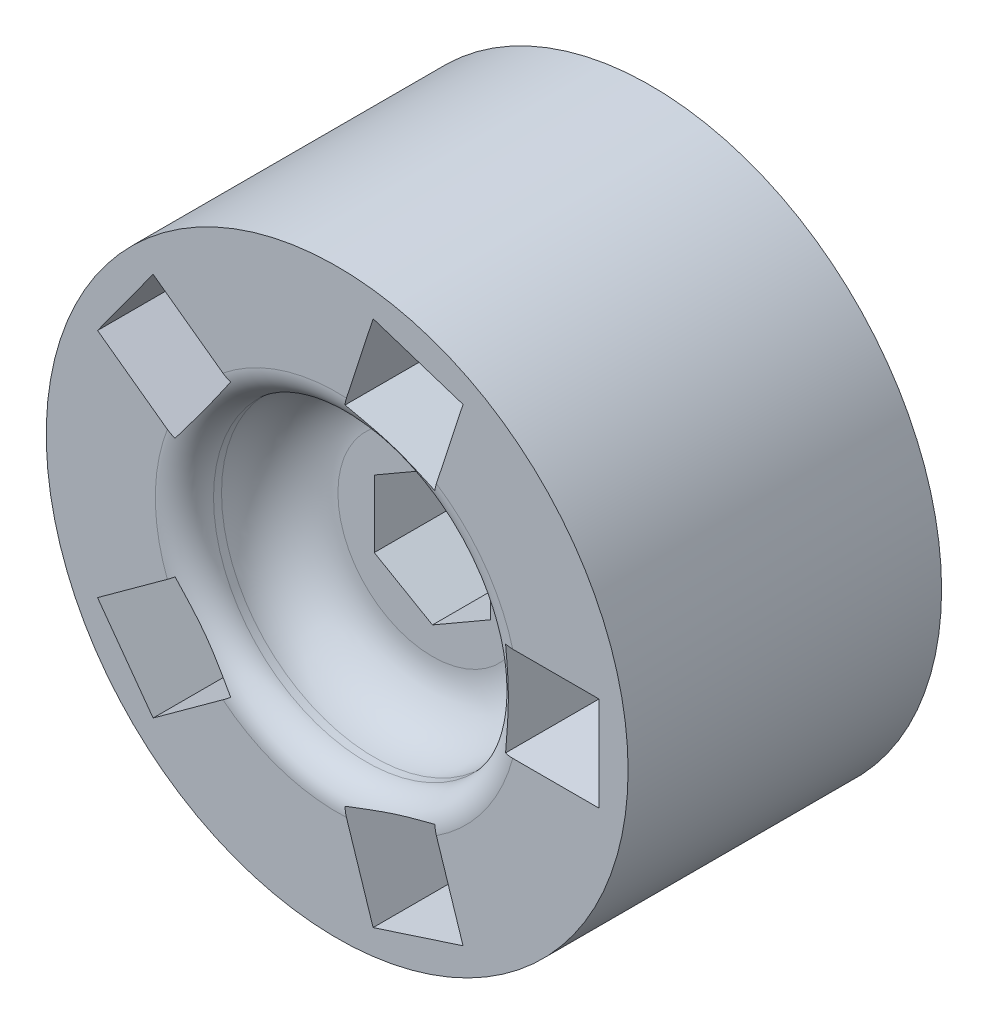
SolidWorks part; units mm, degrees
ref_plane "Front Plane" through (0, 0, 0) normal (0, 0, 1) x (1, 0, 0)
ref_plane "Top Plane" through (0, 0, 0) normal (0, 1, 0) x (1, 0, 0)
ref_plane "Right Plane" through (0, 0, 0) normal (1, 0, 0) x (0, 0, -1)
sketch "Sketch1" plane through (0, 0, 0) normal (0, 0, 1) x (1, 0, 0)
  circle A0 centre (-11.8226, 14.5298) radius 20
  circle A1 centre (-11.8226, 14.5298) radius 1
  dimension "D1" = 40
  dimension "D2" = 2
extrude "Boss-Extrude1" add sketch "Sketch1" along normal blind 21.55
hole_wizard "Tap Drill for M5x0.8 Tap1" positions "Sketch2" profile "Sketch3" hole size "M5x0.8" standard "ANSI Metric"
sketch "Sketch2" plane through (0, 0, 21.55) normal (0, 0, 1) x (1, 0, 0)
  point P0 (-11.8226, 14.5298)
sketch "Sketch3" plane through (-11.8226, 14.5298, 21.55) normal (1, 0, 0) x (0, -1, 0)
  line L0 (0, 0) -> (0, 6.2618)
  line L1 (0, 6.2618) -> (2.1, 5)
  line L2 (2.1, 5) -> (2.1, 0)
  line L5 (2.1, 0) -> (0, 0)
  line L10 (0, 6.2618) -> (-2.1, 5) construction
  line L11 (0, -6.35) -> (0, 107.95) construction
  dimension "Hole Dia." = 4.2
  dimension "Hole Depth" = 5
  dimension "Drill Angle" = 118
sketch "Sketch4" plane through (0, 0, 21.55) normal (0, 0, 1) x (1, 0, 0)
  line L1 (6.1774, 17.7798) -> (-0.3226, 17.7798)
  line L2 (6.1774, 17.7798) -> (6.1774, 11.2798)
  line L3 (6.1774, 11.2798) -> (-0.3226, 11.2798)
  line L4 (-0.3226, 17.7798) -> (-0.3226, 11.2798)
  circle A0 centre (-11.8226, 14.5298) radius 1 construction
  circle A1 centre (-11.8226, 14.5298) radius 20 construction
  dimension "D1" = 6.5
  dimension "D2" = 6.5
  dimension "D3" = 3.25
  dimension "D4" = 18
extrude "Cut-Extrude1" cut sketch "Sketch4" against normal offset from surface (19.05 mm away) 2.5 up to face at (8.1774, 14.5298, 0)
ref_axis "Axis1" through (-11.8226, 14.5298, 21.55) along (0, 0, -1)
pattern_circular "CirPattern1" count 5 over 360 about axis through (-11.8226, 14.5298, 21.55) along (0, 0, -1) of "Cut-Extrude1"
sketch "Sketch5" plane through (0, 0, 0) normal (0, 0, -1) x (-1, 0, 0)
  circle A0 centre (11.8226, 14.5298) radius 5
  circle A1 centre (11.8226, 14.5298) radius 6
  dimension "D1" = 10
  dimension "D2" = 12
extrude "Cut-Extrude2" cut sketch "Sketch5" against normal blind 1
fillet "Fillet3" radius 0.5 2 edges at (-16.8226, 14.5298, 1) (-17.8226, 14.5298, 1)
sketch "Sketch6" plane through (0, 0, 21.55) normal (0, 0, 1) x (1, 0, 0)
  line L0 (-15.8226, 16.8388) -> (-11.8226, 19.1465)
  line L1 (-7.8226, 12.2208) -> (-15.8226, 12.2208)
  line L2 (-7.8226, 12.2208) -> (-7.8226, 16.8388)
  line L3 (-7.8226, 16.8388) -> (-15.8226, 16.8388)
  line L4 (-15.8226, 12.2208) -> (-15.8226, 16.8388)
  line L5 (-7.8226, 12.2208) -> (-15.8226, 16.8388) construction
  line L6 (-7.8226, 16.8388) -> (-15.8226, 12.2208) construction
  line L7 (-11.8226, 19.1465) -> (-7.8226, 16.8388)
  line L8 (-7.8226, 12.2208) -> (-11.8226, 9.913)
  line L9 (-11.8226, 9.913) -> (-15.8226, 12.2208)
  point P0 (-11.8226, 14.5298)
  circle M25 centre (-11.8226, 14.5298) radius 2.1
  dimension "D1" = 8
  dimension "D2" = 4.618
  dimension "D3" = 4.618
  dimension "D4" = 4.618
  dimension "D5" = 4.618
  dimension "D6" = 4.618
extrude "Cut-Extrude3" cut sketch "Sketch6" against normal up to surface (21.55 mm away) contours L4 L1 L2 L3 M25 | M25 | L7 L0 L3 | L9 L8 L1 region at (-11.8226, 17.608, 21.55) region at (-11.8226, 16.7464, 21.55) region at (-11.8226, 11.4515, 21.55) region at (-11.8226, 14.5298, 21.55) up to face at (-17.8226, 14.5298, 0)
sketch "Sketch7" plane through (0, 0, 21.55) normal (0, 0, 1) x (1, 0, 0)
  circle A0 centre (-11.8226, 14.5298) radius 10.5
  dimension "D1" = 21
extrude "Cut-Extrude4" cut sketch "Sketch7" against normal offset from surface (6.55 mm away) 15 up to face at (-17.8226, 14.5298, 0)
fillet "Fillet4" radius 2 1 edges at (-1.3226, 14.5298, 21.55)
fillet "Fillet5" radius 4 1 edges at (-1.3226, 14.5298, 15)
equation "\"D2@Sketch4\"=6.5"
equation "\"D3@Sketch4\"=6.5/2"
equation "\"oringdiameter\"= 11"
equation "\"oringthickness\"= 2"
equation "\"D2@Sketch5\"=\"oringdiameter\" + \"oringthickness\"/2"
equation "\"D1@Sketch5\"=\"oringdiameter\" - \"oringthickness\"/2"
equation "\"D1@Cut-Extrude2\"= \"oringthickness\"/2"
equation "\"D1@Boss-Extrude1\"= 2.5 + (25.4*3/4)"
